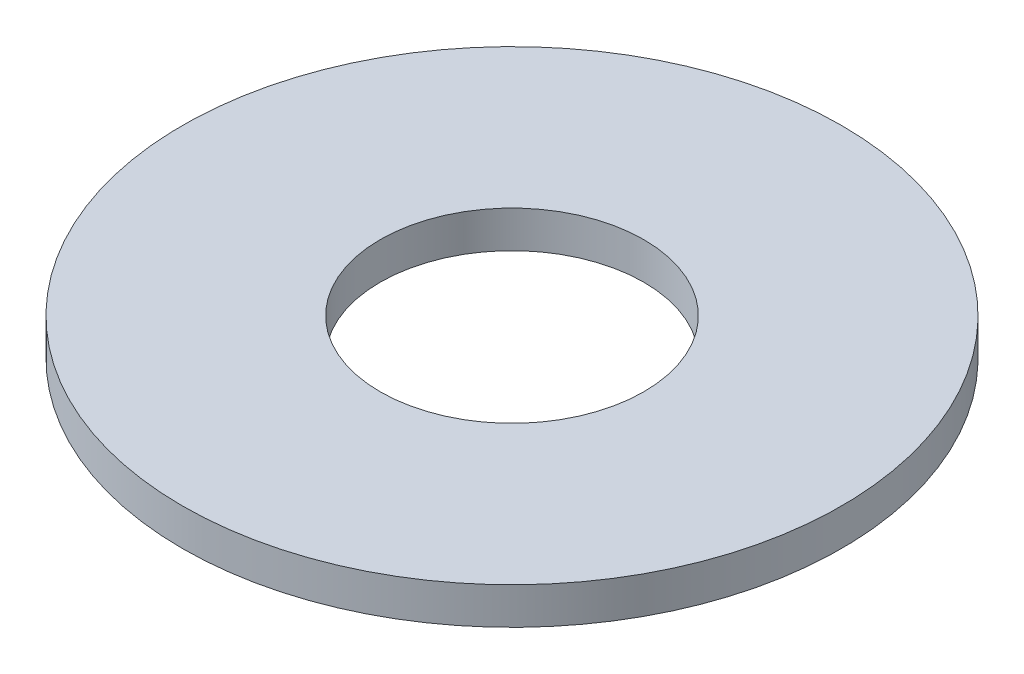
SolidWorks part; units mm, degrees
ref_plane "Front Plane" through (0, 0, 0) normal (0, 0, 1) x (1, 0, 0)
ref_plane "Top Plane" through (0, 0, 0) normal (0, 1, 0) x (1, 0, 0)
ref_plane "Right Plane" through (0, 0, 0) normal (1, 0, 0) x (0, 0, -1)
sketch "Sketch1" plane through (0, 0, 0) normal (0, 1, 0) x (1, 0, 0)
  circle A0 centre (0, 0) radius 62.5
  dimension "FLANGE_OD" = 125
extrude "Boss-Extrude1" add sketch "Sketch1" along normal blind 7
sketch "Sketch2" plane through (0, 0, 0) normal (0, 1, 0) x (1, 0, 0)
  circle A0 centre (0, 0) radius 25
  dimension "BORE_D" = 50
extrude "Cut-Extrude1" cut sketch "Sketch2" along normal through all
sketch "Sketch3" plane through (0, 7, 0) normal (0, 1, 0) x (1, 0, 0)
  circle A0 centre (0, 0) radius 18.7537 construction
  circle A1 centre (-18.7537, 0) radius 5.6327
  dimension "BOLT_D" = 11.2654
  dimension "BOLT_PCD" = 37.5075
extrude "Cut-Extrude2" cut sketch "Sketch3" against normal blind 5.4464 rebuild error yes
pattern_circular "CirPattern1" count 5 over 360 rebuild error yes
